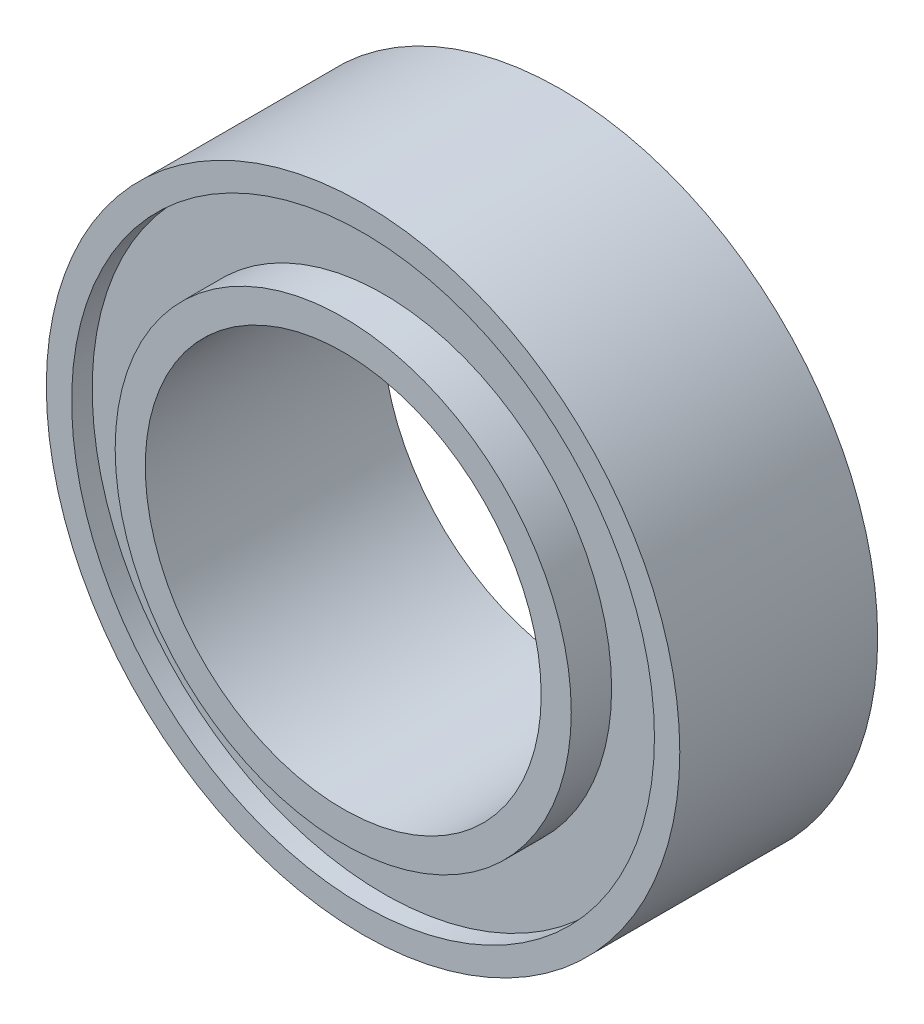
SolidWorks part; units mm, degrees
material "Alloy Steel"
ref_plane "Front Plane" through (0, 0, 0) normal (0, 0, 1) x (1, 0, 0)
ref_plane "Top Plane" through (0, 0, 0) normal (0, 1, 0) x (1, 0, 0)
ref_plane "Right Plane" through (0, 0, 0) normal (1, 0, 0) x (0, 0, -1)
sketch "Sketch1" plane through (0, 0, 0) normal (0, 0, 1) x (1, 0, 0)
  circle A0 centre (0, 0) radius 6.35
  circle A1 centre (0, 0) radius 3.9688
  circle A2 centre (0, 0) radius 4.572
  circle A3 centre (0, 0) radius 5.842
extrude "Boss-Extrude1" add sketch "Sketch1" along normal blind 3.9675 contours A0 A3 region at (-6.1704, 0, 0)
extrude "Boss-Extrude2" add sketch "Sketch1<3>" along normal blind 4.365 and the other way blind 0.3975 separate body contours A2 A1 region at (-4.4427, 0, 0)
sketch "Sketch1<3>" plane through (0, 0, 0) normal (0, 0, 1) x (1, 0, 0) same geometry as "Sketch1"
extrude "Boss-Extrude3" add sketch "Sketch1<4>" along normal blind 3.1445 from offset 0.4115 contours A3 A2 region at (-5.6768, 0, 0)
sketch "Sketch1<4>" plane through (0, 0, 0) normal (0, 0, 1) x (1, 0, 0) same geometry as "Sketch1"
